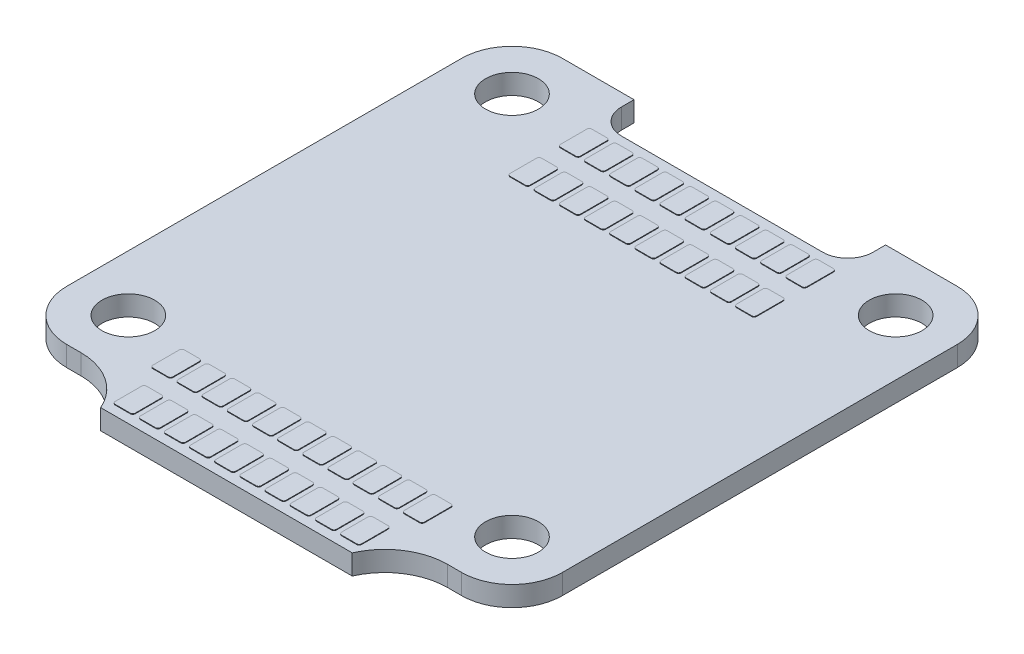
SolidWorks part; units mm, degrees
ref_plane "Front Plane" through (0, 0, 0) normal (0, 0, 1) x (1, 0, 0)
ref_plane "Top Plane" through (0, 0, 0) normal (0, 1, 0) x (1, 0, 0)
ref_plane "Right Plane" through (0, 0, 0) normal (1, 0, 0) x (0, 0, -1)
sketch "Sketch1" plane through (0, 0, 0) normal (0, 1, 0) x (1, 0, 0)
  line L0 (-10, 19.7) -> (-10, 18.7)
  line L1 (-15.7, 19.7) -> (15.7, 19.7)
  line L2 (-19.7, 15.7) -> (-19.7, -15.7)
  line L3 (-15.7, -19.7) -> (15.7, -19.7)
  line L4 (19.7, 15.7) -> (19.7, -15.7)
  line L5 (0, -19.7) -> (0, 19.7) construction
  line L6 (-19.7, 0) -> (19.7, 0) construction
  line L7 (-15.25, 15.25) -> (15.25, 15.25) construction
  line L8 (-15.25, 15.25) -> (-15.25, -15.25) construction
  line L9 (-15.25, -15.25) -> (15.25, -15.25) construction
  line L10 (15.25, 15.25) -> (15.25, -15.25) construction
  line L11 (0, -15.25) -> (0, 15.25) construction
  line L12 (-15.25, 0) -> (15.25, 0) construction
  line L13 (-8, 16.7) -> (8, 16.7)
  line L14 (10, 18.7) -> (10, 19.7)
  line L15 (-10, -19.7) -> (-10, -22.7)
  line L16 (-10, -22.7) -> (10, -22.7)
  line L17 (10, -22.7) -> (10, -19.7)
  line L18 (0, -19.7) -> (0, -22.7) construction
  arc A0 (-19.7, -15.7) -> (-15.7, -19.7) centre (-15.7, -15.7) ccw
  arc A1 (15.7, -19.7) -> (19.7, -15.7) centre (15.7, -15.7) ccw
  arc A2 (19.7, 15.7) -> (15.7, 19.7) centre (15.7, 15.7) ccw
  arc A3 (-15.7, 19.7) -> (-19.7, 15.7) centre (-15.7, 15.7) ccw
  circle A4 centre (-15.25, 15.25) radius 2.1
  circle A5 centre (15.25, 15.25) radius 2.1
  circle A6 centre (15.25, -15.25) radius 2.1
  circle A7 centre (-15.25, -15.25) radius 2.1
  arc A8 (10, 18.7) -> (8, 16.7) centre (8, 18.7) cw
  arc A9 (-8, 16.7) -> (-10, 18.7) centre (-8, 18.7) cw
  point P0 (0, 0)
  point P13 (0, 0)
  point P23 (0, 16.7)
  point P33 (0, -22.7)
  dimension "D3" = 4
  dimension "D5" = 4.2
  dimension "D8" = 2
  dimension "D2" = 39.4
  dimension "D1" = 39.4
  dimension "D4" = 30.5
  dimension "D6" = 3
  dimension "D7" = 10
  dimension "D9" = 3
extrude "Boss-Extrude1" add sketch "Sketch1" along normal mid plane 1.6 contours L13 A9 L0 L1 A3 L2 A0 L3 A1 L4 A2 L14 A8 A7 A6 A5 A4 | L16 L17 L3 L15 region at (0, 0, 0.7457) region at (0, 0, 21.2)
fillet "Fillet1" radius 5 2 edges at (-10, 0, 19.7) (10, 0, 19.7)
sketch "Sketch2" plane through (0, 0.8, 0) normal (0, 1, 0) x (1, 0, 0)
  line L0 (0, 0) -> (0, -22.7) construction
  line L1 (-10, -22.7) -> (10, -22.7) construction
  line L2 (-2.2, -19.45) -> (-2.2, -21.95)
  line L3 (-0.8, -15.45) -> (0.8, -15.45)
  line L4 (-0.8, -15.45) -> (-0.8, -17.95)
  line L5 (-0.8, -17.95) -> (0.8, -17.95)
  line L6 (0.8, -15.45) -> (0.8, -17.95)
  line L7 (0, -17.95) -> (0, -15.45) construction
  line L8 (-0.8, -16.7) -> (0.8, -16.7) construction
  line L9 (-1.8, -19.45) -> (-0.2, -19.45)
  line L10 (-1.8, -19.45) -> (-1.8, -21.95)
  line L11 (-1.8, -21.95) -> (-0.2, -21.95)
  line L12 (-0.2, -19.45) -> (-0.2, -21.95)
  line L13 (-1, -21.95) -> (-1, -19.45) construction
  line L14 (-1.8, -20.7) -> (-0.2, -20.7) construction
  line L15 (-3.8, -21.95) -> (-2.2, -21.95)
  line L16 (-3.8, -19.45) -> (-3.8, -21.95)
  line L17 (-3.8, -19.45) -> (-2.2, -19.45)
  line L18 (-4.2, -19.45) -> (-4.2, -21.95)
  line L19 (-5.8, -21.95) -> (-4.2, -21.95)
  line L20 (-5.8, -19.45) -> (-5.8, -21.95)
  line L21 (-5.8, -19.45) -> (-4.2, -19.45)
  line L22 (-6.2, -19.45) -> (-6.2, -21.95)
  line L23 (-7.8, -21.95) -> (-6.2, -21.95)
  line L24 (-7.8, -19.45) -> (-7.8, -21.95)
  line L25 (-7.8, -19.45) -> (-6.2, -19.45)
  line L26 (-8.2, -19.45) -> (-8.2, -21.95)
  line L27 (-9.8, -21.95) -> (-8.2, -21.95)
  line L28 (-9.8, -19.45) -> (-9.8, -21.95)
  line L29 (-9.8, -19.45) -> (-8.2, -19.45)
  line L30 (-0.2, -19.45) -> (-2.2, -19.45) construction
  line L31 (-2.8, -15.45) -> (-2.8, -17.95)
  line L32 (-2.8, -15.45) -> (-1.2, -15.45)
  line L33 (-1.2, -15.45) -> (-1.2, -17.95)
  line L34 (-2.8, -17.95) -> (-1.2, -17.95)
  line L35 (-4.8, -15.45) -> (-4.8, -17.95)
  line L36 (-4.8, -15.45) -> (-3.2, -15.45)
  line L37 (-3.2, -15.45) -> (-3.2, -17.95)
  line L38 (-4.8, -17.95) -> (-3.2, -17.95)
  line L39 (-6.8, -15.45) -> (-6.8, -17.95)
  line L40 (-6.8, -15.45) -> (-5.2, -15.45)
  line L41 (-5.2, -15.45) -> (-5.2, -17.95)
  line L42 (-6.8, -17.95) -> (-5.2, -17.95)
  line L43 (-8.8, -15.45) -> (-8.8, -17.95)
  line L44 (-8.8, -15.45) -> (-7.2, -15.45)
  line L45 (-7.2, -15.45) -> (-7.2, -17.95)
  line L46 (-8.8, -17.95) -> (-7.2, -17.95)
  line L47 (-10.8, -15.45) -> (-10.8, -17.95)
  line L48 (-10.8, -15.45) -> (-9.2, -15.45)
  line L49 (-9.2, -15.45) -> (-9.2, -17.95)
  line L50 (-10.8, -17.95) -> (-9.2, -17.95)
  line L51 (-0.8, -15.45) -> (-2.8, -15.45) construction
  line L52 (1.8, -21.95) -> (0.2, -21.95)
  line L53 (0.2, -19.45) -> (0.2, -21.95)
  line L54 (1.8, -19.45) -> (0.2, -19.45)
  line L55 (10.8, -17.95) -> (9.2, -17.95)
  line L56 (9.2, -15.45) -> (9.2, -17.95)
  line L57 (10.8, -15.45) -> (9.2, -15.45)
  line L58 (10.8, -15.45) -> (10.8, -17.95)
  line L59 (8.8, -17.95) -> (7.2, -17.95)
  line L60 (7.2, -15.45) -> (7.2, -17.95)
  line L61 (8.8, -15.45) -> (7.2, -15.45)
  line L62 (8.8, -15.45) -> (8.8, -17.95)
  line L63 (6.8, -17.95) -> (5.2, -17.95)
  line L64 (5.2, -15.45) -> (5.2, -17.95)
  line L65 (6.8, -15.45) -> (5.2, -15.45)
  line L66 (6.8, -15.45) -> (6.8, -17.95)
  line L67 (4.8, -17.95) -> (3.2, -17.95)
  line L68 (3.2, -15.45) -> (3.2, -17.95)
  line L69 (4.8, -15.45) -> (3.2, -15.45)
  line L70 (4.8, -15.45) -> (4.8, -17.95)
  line L71 (2.8, -17.95) -> (1.2, -17.95)
  line L72 (1.2, -15.45) -> (1.2, -17.95)
  line L73 (2.8, -15.45) -> (1.2, -15.45)
  line L74 (2.8, -15.45) -> (2.8, -17.95)
  line L75 (9.8, -19.45) -> (8.2, -19.45)
  line L76 (9.8, -19.45) -> (9.8, -21.95)
  line L77 (9.8, -21.95) -> (8.2, -21.95)
  line L78 (8.2, -19.45) -> (8.2, -21.95)
  line L79 (7.8, -19.45) -> (6.2, -19.45)
  line L80 (7.8, -19.45) -> (7.8, -21.95)
  line L81 (7.8, -21.95) -> (6.2, -21.95)
  line L82 (6.2, -19.45) -> (6.2, -21.95)
  line L83 (5.8, -19.45) -> (4.2, -19.45)
  line L84 (5.8, -19.45) -> (5.8, -21.95)
  line L85 (5.8, -21.95) -> (4.2, -21.95)
  line L86 (4.2, -19.45) -> (4.2, -21.95)
  line L87 (3.8, -19.45) -> (2.2, -19.45)
  line L88 (3.8, -19.45) -> (3.8, -21.95)
  line L89 (3.8, -21.95) -> (2.2, -21.95)
  line L90 (1.8, -19.45) -> (1.8, -21.95)
  line L91 (2.2, -19.45) -> (2.2, -21.95)
  line L92 (0, 16.7) -> (0, -22.7) construction
  line L93 (-8, 16.7) -> (8, 16.7) construction
  line L94 (0, -3) -> (7.2, -3) construction
  line L95 (-0.2, 13.45) -> (-2.2, 13.45) construction
  line L96 (-1.8, 14.7) -> (-0.2, 14.7) construction
  line L97 (-1, 15.95) -> (-1, 13.45) construction
  line L98 (2.2, 13.45) -> (2.2, 15.95)
  line L99 (1.8, 13.45) -> (1.8, 15.95)
  line L100 (3.8, 15.95) -> (2.2, 15.95)
  line L101 (3.8, 13.45) -> (3.8, 15.95)
  line L102 (3.8, 13.45) -> (2.2, 13.45)
  line L103 (4.2, 13.45) -> (4.2, 15.95)
  line L104 (5.8, 15.95) -> (4.2, 15.95)
  line L105 (5.8, 13.45) -> (5.8, 15.95)
  line L106 (5.8, 13.45) -> (4.2, 13.45)
  line L107 (6.2, 13.45) -> (6.2, 15.95)
  line L108 (7.8, 15.95) -> (6.2, 15.95)
  line L109 (7.8, 13.45) -> (7.8, 15.95)
  line L110 (7.8, 13.45) -> (6.2, 13.45)
  line L111 (8.2, 13.45) -> (8.2, 15.95)
  line L112 (9.8, 15.95) -> (8.2, 15.95)
  line L113 (9.8, 13.45) -> (9.8, 15.95)
  line L114 (9.8, 13.45) -> (8.2, 13.45)
  line L115 (1.8, 13.45) -> (0.2, 13.45)
  line L116 (0.2, 13.45) -> (0.2, 15.95)
  line L117 (1.8, 15.95) -> (0.2, 15.95)
  line L118 (-9.8, 13.45) -> (-8.2, 13.45)
  line L119 (-9.8, 13.45) -> (-9.8, 15.95)
  line L120 (-9.8, 15.95) -> (-8.2, 15.95)
  line L121 (-8.2, 13.45) -> (-8.2, 15.95)
  line L122 (-7.8, 13.45) -> (-6.2, 13.45)
  line L123 (-7.8, 13.45) -> (-7.8, 15.95)
  line L124 (-7.8, 15.95) -> (-6.2, 15.95)
  line L125 (-6.2, 13.45) -> (-6.2, 15.95)
  line L126 (-5.8, 13.45) -> (-4.2, 13.45)
  line L127 (-5.8, 13.45) -> (-5.8, 15.95)
  line L128 (-5.8, 15.95) -> (-4.2, 15.95)
  line L129 (-4.2, 13.45) -> (-4.2, 15.95)
  line L130 (-3.8, 13.45) -> (-2.2, 13.45)
  line L131 (-3.8, 13.45) -> (-3.8, 15.95)
  line L132 (-3.8, 15.95) -> (-2.2, 15.95)
  line L133 (-0.2, 13.45) -> (-0.2, 15.95)
  line L134 (-1.8, 15.95) -> (-0.2, 15.95)
  line L135 (-1.8, 13.45) -> (-1.8, 15.95)
  line L136 (-1.8, 13.45) -> (-0.2, 13.45)
  line L137 (-2.2, 13.45) -> (-2.2, 15.95)
  line L138 (0, 12.7) -> (4.8, 12.7) construction
  line L139 (-9.8, 9.45) -> (-8.2, 9.45)
  line L140 (-9.8, 11.95) -> (-8.2, 11.95)
  line L141 (-9.8, 11.95) -> (-9.8, 9.45)
  line L142 (-1, 9.45) -> (-1, 11.95) construction
  line L143 (-1.8, 10.7) -> (-0.2, 10.7) construction
  line L144 (-0.2, 11.95) -> (-2.2, 11.95) construction
  line L145 (-2.2, 11.95) -> (-2.2, 9.45)
  line L146 (-1.8, 11.95) -> (-0.2, 11.95)
  line L147 (-1.8, 11.95) -> (-1.8, 9.45)
  line L148 (-1.8, 9.45) -> (-0.2, 9.45)
  line L149 (-0.2, 11.95) -> (-0.2, 9.45)
  line L150 (-3.8, 9.45) -> (-2.2, 9.45)
  line L151 (-3.8, 11.95) -> (-3.8, 9.45)
  line L152 (-3.8, 11.95) -> (-2.2, 11.95)
  line L153 (-4.2, 11.95) -> (-4.2, 9.45)
  line L154 (-5.8, 9.45) -> (-4.2, 9.45)
  line L155 (-5.8, 11.95) -> (-5.8, 9.45)
  line L156 (-5.8, 11.95) -> (-4.2, 11.95)
  line L157 (-6.2, 11.95) -> (-6.2, 9.45)
  line L158 (-7.8, 9.45) -> (-6.2, 9.45)
  line L159 (-7.8, 11.95) -> (-7.8, 9.45)
  line L160 (-7.8, 11.95) -> (-6.2, 11.95)
  line L161 (-8.2, 11.95) -> (-8.2, 9.45)
  line L162 (1.8, 9.45) -> (0.2, 9.45)
  line L163 (0.2, 11.95) -> (0.2, 9.45)
  line L164 (1.8, 11.95) -> (0.2, 11.95)
  line L165 (9.8, 11.95) -> (8.2, 11.95)
  line L166 (9.8, 11.95) -> (9.8, 9.45)
  line L167 (9.8, 9.45) -> (8.2, 9.45)
  line L168 (8.2, 11.95) -> (8.2, 9.45)
  line L169 (7.8, 11.95) -> (6.2, 11.95)
  line L170 (7.8, 11.95) -> (7.8, 9.45)
  line L171 (7.8, 9.45) -> (6.2, 9.45)
  line L172 (6.2, 11.95) -> (6.2, 9.45)
  line L173 (5.8, 11.95) -> (4.2, 11.95)
  line L174 (5.8, 11.95) -> (5.8, 9.45)
  line L175 (5.8, 9.45) -> (4.2, 9.45)
  line L176 (4.2, 11.95) -> (4.2, 9.45)
  line L177 (3.8, 11.95) -> (2.2, 11.95)
  line L178 (3.8, 11.95) -> (3.8, 9.45)
  line L179 (3.8, 9.45) -> (2.2, 9.45)
  line L180 (1.8, 11.95) -> (1.8, 9.45)
  line L181 (2.2, 11.95) -> (2.2, 9.45)
  point P5 (0, -16.7)
  point P9 (-1, -20.7)
  point P147 (-1, 14.7)
  point P194 (-1, 10.7)
  dimension "D1" = 2.5
  dimension "D2" = 1.6
  dimension "D3" = 6
  dimension "D4" = 2
  dimension "D5" = 1
  dimension "D7" = 2
  dimension "D9" = 2
  dimension "D10" = 0.75
  dimension "D6" = 5
  dimension "D8" = 6
extrude "Boss-Extrude2" add sketch "Sketch2" along normal mid plane 0.1
fillet "Fillet2" radius 0.2 164 edges at (2.2, 0.825, 19.45) (2.2, 0.825, 21.95) (3.8, 0.825, 21.95) (3.8, 0.825, 19.45) (4.2, 0.825, 19.45) (4.2, 0.825, 21.95) (5.8, 0.825, 21.95) (5.8, 0.825, 19.45) (6.2, 0.825, 19.45) (6.2, 0.825, 21.95) (7.8, 0.825, 21.95) (7.8, 0.825, 19.45) (8.2, 0.825, 19.45) (8.2, 0.825, 21.95) (9.8, 0.825, 21.95) (9.8, 0.825, 19.45) (1.2, 0.825, 15.45) (1.2, 0.825, 17.95) (2.8, 0.825, 17.95) (2.8, 0.825, 15.45) (3.2, 0.825, 15.45) (3.2, 0.825, 17.95) (4.8, 0.825, 17.95) (4.8, 0.825, 15.45) (5.2, 0.825, 15.45) (5.2, 0.825, 17.95) (6.8, 0.825, 17.95) (6.8, 0.825, 15.45) (7.2, 0.825, 15.45) (7.2, 0.825, 17.95) (8.8, 0.825, 17.95) (8.8, 0.825, 15.45) (9.2, 0.825, 15.45) (9.2, 0.825, 17.95) (10.8, 0.825, 17.95) (10.8, 0.825, 15.45) (-9.2, 0.825, 15.45) (-10.8, 0.825, 15.45) (-10.8, 0.825, 17.95) (-9.2, 0.825, 17.95) (-7.2, 0.825, 15.45) (-8.8, 0.825, 15.45) (-8.8, 0.825, 17.95) (-7.2, 0.825, 17.95) (-5.2, 0.825, 15.45) (-6.8, 0.825, 15.45) (-6.8, 0.825, 17.95) (-5.2, 0.825, 17.95) (-3.2, 0.825, 15.45) (-4.8, 0.825, 15.45) (-4.8, 0.825, 17.95) (-3.2, 0.825, 17.95) (0.2, 0.825, 19.45) (0.2, 0.825, 21.95) (1.8, 0.825, 21.95) (1.8, 0.825, 19.45) (-8.2, 0.825, 19.45) (-9.8, 0.825, 19.45) (-8.2, 0.825, 21.95) (-6.2, 0.825, 19.45) (-7.8, 0.825, 19.45) (-7.8, 0.825, 21.95) (-6.2, 0.825, 21.95) (-4.2, 0.825, 19.45) (-5.8, 0.825, 19.45) (-5.8, 0.825, 21.95) (-4.2, 0.825, 21.95) (-1.2, 0.825, 15.45) (-2.8, 0.825, 15.45) (-2.8, 0.825, 17.95) (-1.2, 0.825, 17.95) (-2.2, 0.825, 19.45) (-3.8, 0.825, 19.45) (-3.8, 0.825, 21.95) (-2.2, 0.825, 21.95) (-1.8, 0.825, 19.45) (-1.8, 0.825, 21.95) (-0.2, 0.825, 21.95) (-0.2, 0.825, 19.45) (-0.8, 0.825, 15.45) (-0.8, 0.825, 17.95) (0.8, 0.825, 17.95) (0.8, 0.825, 15.45) (-9.8, 0.825, 21.95) (-7.8, 0.825, -9.45) (-8.2, 0.825, -9.45) (-8.2, 0.825, -11.95) (-9.8, 0.825, -11.95) (-9.8, 0.825, -9.45) (2.2, 0.825, -11.95) (2.2, 0.825, -9.45) (3.8, 0.825, -9.45) (3.8, 0.825, -11.95) (4.2, 0.825, -11.95) (4.2, 0.825, -9.45) (5.8, 0.825, -9.45) (5.8, 0.825, -11.95) (6.2, 0.825, -11.95) (6.2, 0.825, -9.45) (7.8, 0.825, -9.45) (7.8, 0.825, -11.95) (8.2, 0.825, -11.95) (8.2, 0.825, -9.45) (9.8, 0.825, -9.45) (9.8, 0.825, -11.95) (0.2, 0.825, -11.95) (0.2, 0.825, -9.45) (1.8, 0.825, -9.45) (1.8, 0.825, -11.95) (-6.2, 0.825, -9.45) (-6.2, 0.825, -11.95) (-7.8, 0.825, -11.95) (-5.8, 0.825, -9.45) (-4.2, 0.825, -9.45) (-4.2, 0.825, -11.95) (-5.8, 0.825, -11.95) (-3.8, 0.825, -9.45) (-2.2, 0.825, -9.45) (-2.2, 0.825, -11.95) (-3.8, 0.825, -11.95) (-1.8, 0.825, -11.95) (-1.8, 0.825, -9.45) (-0.2, 0.825, -9.45) (-0.2, 0.825, -11.95) (-4.2, 0.825, -13.45) (-4.2, 0.825, -15.95) (-5.8, 0.825, -15.95) (-5.8, 0.825, -13.45) (-6.2, 0.825, -13.45) (-6.2, 0.825, -15.95) (-7.8, 0.825, -15.95) (-7.8, 0.825, -13.45) (-8.2, 0.825, -13.45) (-8.2, 0.825, -15.95) (-9.8, 0.825, -15.95) (-9.8, 0.825, -13.45) (9.8, 0.825, -15.95) (8.2, 0.825, -15.95) (8.2, 0.825, -13.45) (9.8, 0.825, -13.45) (7.8, 0.825, -15.95) (6.2, 0.825, -15.95) (6.2, 0.825, -13.45) (7.8, 0.825, -13.45) (5.8, 0.825, -15.95) (4.2, 0.825, -15.95) (4.2, 0.825, -13.45) (5.8, 0.825, -13.45) (1.8, 0.825, -15.95) (0.2, 0.825, -15.95) (0.2, 0.825, -13.45) (1.8, 0.825, -13.45) (3.8, 0.825, -15.95) (2.2, 0.825, -15.95) (2.2, 0.825, -13.45) (3.8, 0.825, -13.45) (-3.8, 0.825, -15.95) (-3.8, 0.825, -13.45) (-2.2, 0.825, -13.45) (-2.2, 0.825, -15.95) (-0.2, 0.825, -15.95) (-1.8, 0.825, -15.95) (-1.8, 0.825, -13.45) (-0.2, 0.825, -13.45)
equation "\"D1@Sketch1\"=\"D2@Sketch1\""
